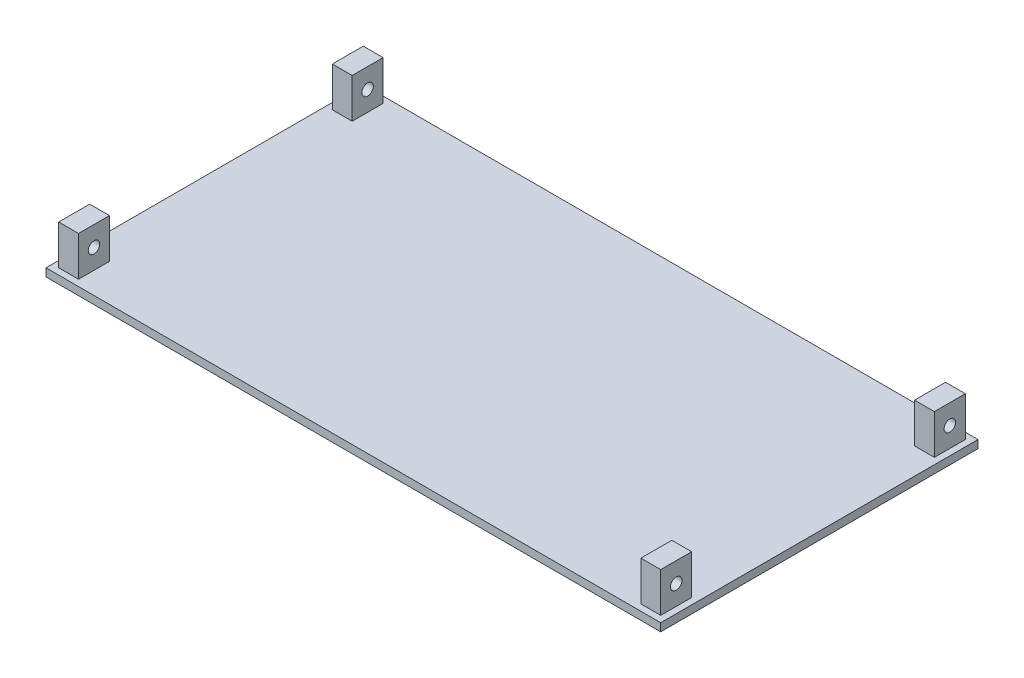
SolidWorks part; units mm, degrees
ref_plane "Front Plane" through (0, 0, 0) normal (0, 0, 1) x (1, 0, 0)
ref_plane "Top Plane" through (0, 0, 0) normal (0, 1, 0) x (1, 0, 0)
ref_plane "Right Plane" through (0, 0, 0) normal (1, 0, 0) x (0, 0, -1)
sketch "Sketch1" plane through (0, 0, 0) normal (0, 1, 0) x (1, 0, 0)
  line L1 (0, 0) -> (-155, 0)
  line L2 (0, 0) -> (0, 80)
  line L3 (0, 80) -> (-155, 80)
  line L4 (-155, 0) -> (-155, 80)
extrude "Boss-Extrude1" add sketch "Sketch1" along normal blind 2
ref_plane "Plane1" through (0, 2, 0) normal (0, 1, 0) x (1, 0, 0)
ref_axis "Axis1" through (-155, 0, -40) along (0.9999, 0.0129, 0)
ref_plane "Plane2" through (0, 0, -40) normal (0, 0, 1) x (0.9999, 0.0129, 0)
sketch "Sketch2" plane through (0, 2, 0) normal (0, 1, 0) x (1, 0, 0)
  line L7 (-148.4, 78.4) -> (-148.4, 70.6)
  line L8 (-153.4, 78.4) -> (-148.4, 78.4)
  line L9 (-153.4, 1.6) -> (-148.4, 1.6)
  line L10 (-153.4, 1.6) -> (-153.4, 9.4)
  line L11 (-153.4, 9.4) -> (-148.4, 9.4)
  line L12 (-148.4, 1.6) -> (-148.4, 9.4)
  line L13 (-153.4, 78.4) -> (-153.4, 70.6)
  line L14 (-153.4, 70.6) -> (-148.4, 70.6)
  line L18 (-6.6, 78.4) -> (-6.6, 70.6)
  line L19 (-1.6, 78.4) -> (-6.6, 78.4)
  line L20 (-1.6, 78.4) -> (-1.6, 70.6)
  line L21 (-1.6, 70.6) -> (-6.6, 70.6)
  line L22 (-1.6, 1.6) -> (-1.6, 9.4)
  line L23 (-1.6, 1.6) -> (-6.6, 1.6)
  line L24 (-6.6, 1.6) -> (-6.6, 9.4)
  line L25 (-1.6, 9.4) -> (-6.6, 9.4)
extrude "Boss-Extrude2" add sketch "Sketch2" along normal blind 10
sketch "Sketch3" plane through (-153.4, 0, 0) normal (-1, 0, 0) x (0, 0, 1)
  circle A0 centre (-5.5, 7) radius 1.45
extrude "Cut-Extrude1" cut sketch "Sketch3" against normal blind 210
sketch "Sketch4" plane through (-1.6, 0, 0) normal (1, 0, 0) x (0, 0, -1)
  circle A0 centre (74.5, 7) radius 1.45
extrude "Cut-Extrude2" cut sketch "Sketch4" against normal blind 210
